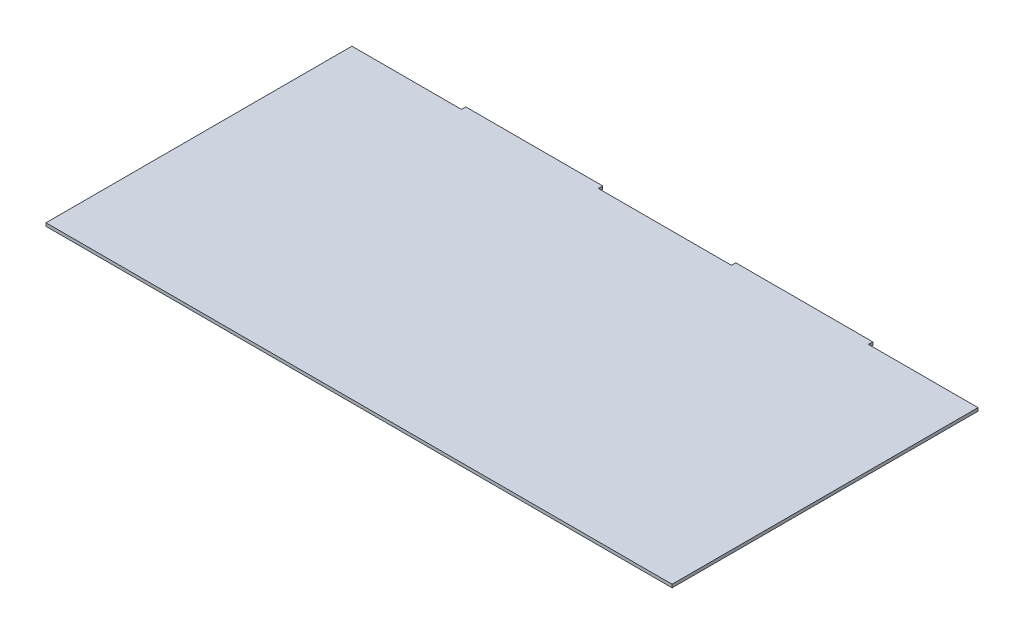
SolidWorks part; units mm, degrees
material "6061-T6 (SS)"
ref_plane "X-Y Datum" through (0, 0, 0) normal (0, 0, 1) x (1, 0, 0)
ref_plane "X-Z Datum" through (0, 0, 0) normal (0, 1, 0) x (1, 0, 0)
ref_plane "Y-Z Datum" through (0, 0, 0) normal (1, 0, 0) x (0, 0, -1)
sketch "Sketch1" plane through (0, 0, 0) normal (0, 0, 1) x (1, 0, 0)
  line L1 (-228.6, -1.143) -> (228.6, -1.143)
  line L2 (-228.6, -1.143) -> (-228.6, 1.143)
  line L3 (-228.6, 1.143) -> (228.6, 1.143)
  line L4 (228.6, -1.143) -> (228.6, 1.143)
  line L5 (-228.6, -1.143) -> (228.6, 1.143) construction
  line L6 (-228.6, 1.143) -> (228.6, -1.143) construction
  point P0 (0, 0)
  dimension "D1" = 2.286
  dimension "D2" = 457.2
extrude "Boss-Extrude1" add sketch "Sketch1" along normal blind 223.38
sketch "Sketch2" plane through (0, 0, 0) normal (0, 0, -1) x (-1, 0, 0)
  line L0 (-228.6, 1.143) -> (228.6, 1.143) construction
  line L2 (-148.6115, 1.143) -> (-148.6115, -1.143)
  line L4 (-48.6115, 1.143) -> (-48.6115, -1.143)
  line L6 (48.6115, 1.143) -> (48.6115, -1.143)
  line L8 (148.6115, 1.143) -> (148.6115, -1.143)
  line L9 (-148.6115, 1.143) -> (-48.6115, 1.143)
  line L10 (-148.6115, 1.143) -> (-148.6115, -1.143)
  line L11 (-148.6115, -1.143) -> (-48.6115, -1.143)
  line L12 (-48.6115, 1.143) -> (-48.6115, -1.143)
  line L13 (228.6, -1.143) -> (-228.6, -1.143) construction
  line L15 (48.6115, 1.143) -> (148.6115, 1.143)
  line L16 (48.6115, 1.143) -> (48.6115, -1.143)
  line L17 (48.6115, -1.143) -> (148.6115, -1.143)
  line L18 (148.6115, 1.143) -> (148.6115, -1.143)
  line M6 (-228.6, -1.143) -> (228.6, -1.143)
  line M8 (228.6, 1.143) -> (-228.6, 1.143)
  dimension "D1" = 100
  dimension "D2" = 100
extrude "Boss-Extrude2" add sketch "Sketch2" along normal blind 3.175 contours L4 L2 M8 M6 | L8 L6 M8 M6 region at (98.6115, 0, 0) region at (-98.6115, 0, 0)
